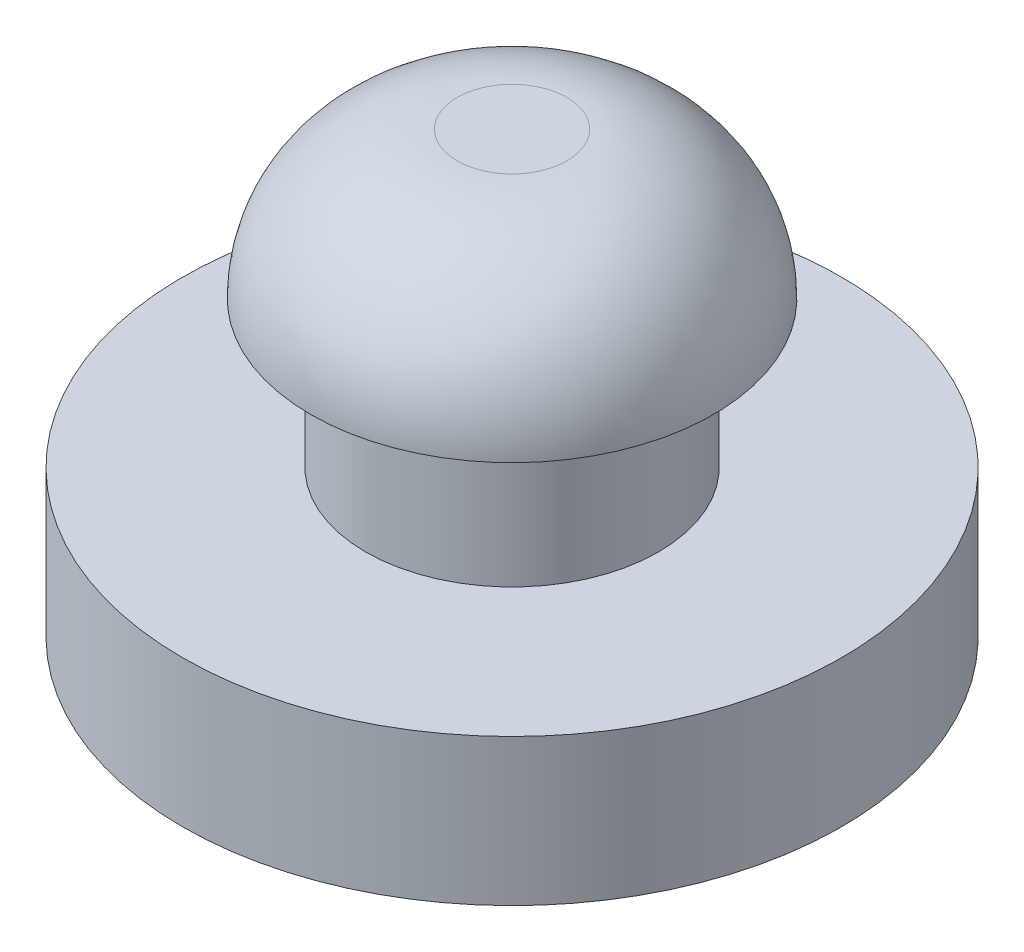
SolidWorks part; units mm, degrees
material "SBR"
ref_plane "Front Plane" through (0, 0, 0) normal (0, 0, 1) x (1, 0, 0)
ref_plane "Top Plane" through (0, 0, 0) normal (0, 1, 0) x (1, 0, 0)
ref_plane "Right Plane" through (0, 0, 0) normal (1, 0, 0) x (0, 0, -1)
sketch "Sketch1" plane through (0, 0, 0) normal (0, 1, 0) x (1, 0, 0)
  circle A0 centre (0, 0) radius 7.1437
  dimension "D1" = 14.2875
extrude "Boss-Extrude1" add sketch "Sketch1" along normal blind 3.175
sketch "Sketch2" plane through (0, 3.175, 0) normal (0, 1, 0) x (1, 0, 0)
  circle A0 centre (0, 0) radius 3.175
  dimension "D1" = 6.35
extrude "Boss-Extrude2" add sketch "Sketch2" along normal blind 3.175
sketch "Sketch3" plane through (0, 6.35, 0) normal (0, 1, 0) x (1, 0, 0)
  circle A0 centre (0, 0) radius 4.3656
  dimension "D1" = 8.7312
extrude "Boss-Extrude3" add sketch "Sketch3" along normal blind 3.175
fillet "Fillet1" radius 3.175 1 edges at (0, 9.525, 4.3656)
